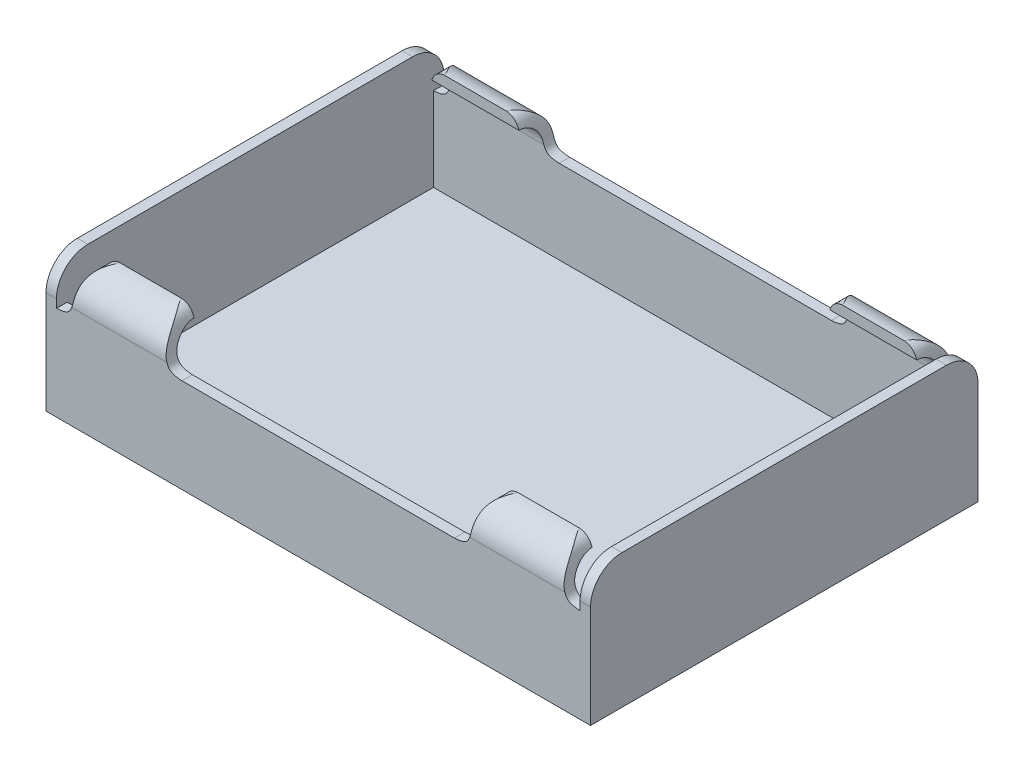
SolidWorks part; units mm, degrees
ref_plane "Front Plane" through (0, 0, 0) normal (0, 0, 1) x (1, 0, 0)
ref_plane "Top Plane" through (0, 0, 0) normal (0, 1, 0) x (1, 0, 0)
ref_plane "Right Plane" through (0, 0, 0) normal (1, 0, 0) x (0, 0, -1)
sketch "Sketch1" plane through (0, 0, 0) normal (0, 1, 0) x (1, 0, 0)
  line L1 (26, 18.5) -> (-26, 18.5)
  line L2 (26, 18.5) -> (26, -18.5)
  line L3 (26, -18.5) -> (-26, -18.5)
  line L4 (-26, 18.5) -> (-26, -18.5)
  line L5 (26, 18.5) -> (-26, -18.5) construction
  line L6 (26, -18.5) -> (-26, 18.5) construction
  point P0 (0, 0)
  dimension "D1" = 52
  dimension "D2" = 37
extrude "Boss-Extrude1" add sketch "Sketch1" along normal blind 12.8
fillet "Fillet1" radius 3 2 edges at (0, 12.8, -18.5) (0, 12.8, 18.5)
shell "Shell2" thickness 1 removed face at (0, 12.8, 0)
sketch "Sketch2" plane through (0, 0, 18.5) normal (0, 0, 1) x (1, 0, 0)
  line L0 (-26, 9) -> (-25, 9) construction
  line L1 (-25, 9) -> (-22, 9) construction
  line L2 (0, 0) -> (0, 12.8) construction
  line L3 (-25, 12.8) -> (25, 12.8) construction
  line L4 (-26, 0) -> (-26, 9) construction
  line L5 (-26, 9.8) -> (-26, 0) construction
  line L6 (-22, 8.8862) -> (-22, 12.8) construction
  line L7 (-25, 9) -> (-25, 12.8)
  line L8 (-25, 12.8) -> (-22, 12.8)
  line L9 (-22, 9) -> (-19, 9) construction
  line L10 (-19, 9) -> (-19, 12.8) construction
  line L13 (-16, 12.8) -> (16, 12.8)
  line L14 (-13, 9) -> (13, 9)
  line L15 (25, 9) -> (25, 12.8)
  line L16 (25, 12.8) -> (22, 12.8)
  spline S0 degree 3 poles (-25, 9) (-24.3376, 9.036) (-22.8508, 9.4615) (-23.7459, 12.54) (-22, 12.8) knots 0 0 0 0 0.249396 1 1 1 1
  spline S1 degree 3 poles (-13, 9) (-13.6624, 9.036) (-15.1492, 9.4615) (-14.2541, 12.54) (-16, 12.8) knots 0 0 0 0 0.249396 1 1 1 1
  spline S2 degree 3 poles (13, 9) (13.6624, 9.036) (15.1492, 9.4615) (14.2541, 12.54) (16, 12.8) knots 0 0 0 0 0.249396 1 1 1 1
  spline S3 degree 3 poles (25, 9) (24.3376, 9.036) (22.8508, 9.4615) (23.7459, 12.54) (22, 12.8) knots 0 0 0 0 0.249396 1 1 1 1
  point P29 (0, 9)
  dimension "D1" = 3
extrude "Cut-Extrude1" cut sketch "Sketch2" against normal through all and the other way through all
